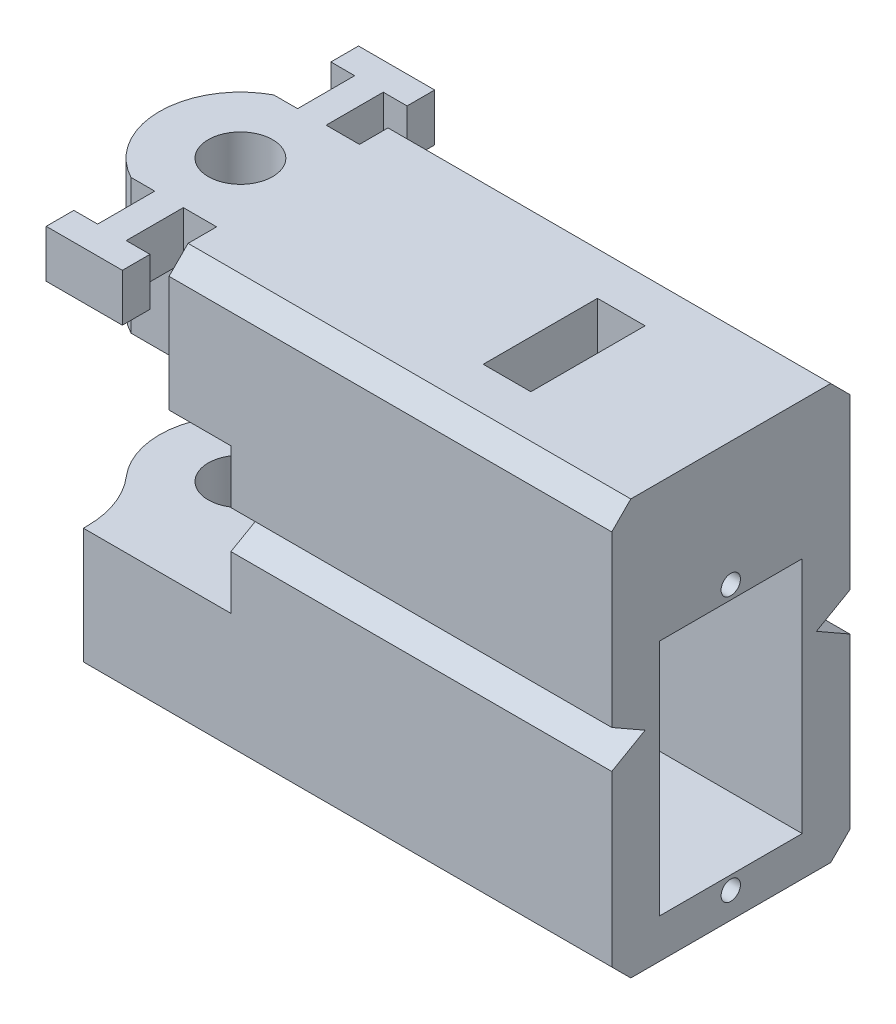
SolidWorks part; units mm, degrees
ref_plane "Front Plane" through (0, 0, 0) normal (0, 0, 1) x (1, 0, 0)
ref_plane "Top Plane" through (0, 0, 0) normal (0, 1, 0) x (1, 0, 0)
ref_plane "Right Plane" through (0, 0, 0) normal (1, 0, 0) x (0, 0, -1)
sketch "Sketch1" plane through (0, 0, 0) normal (1, 0, 0) x (0, 0, -1)
  line L0 (3.5, 21.787) -> (21.5, 21.787) construction
  line L1 (0, 0) -> (25, 0)
  line L2 (0, 0) -> (0, 19.787)
  line L3 (0, 43.574) -> (25, 43.574)
  line L4 (25, 0) -> (25, 19.787)
  line L5 (0, 23.787) -> (3.5, 21.787)
  line L6 (0, 19.787) -> (3.5, 21.787)
  line L7 (12.5, 43.574) -> (12.5, 0) construction
  line L8 (25, 23.787) -> (21.5, 21.787)
  line L9 (25, 19.787) -> (21.5, 21.787)
  line L10 (0, 23.787) -> (0, 43.574)
  line L11 (25, 23.787) -> (25, 43.574)
  point P6 (12.5, 21.787)
  dimension "D1" = 43.574
  dimension "D2" = 25
  dimension "D3" = 4
  dimension "D4" = 18
extrude "Boss-Extrude1" add sketch "Sketch1" along normal blind 55.5
chamfer "Chamfer1" distance 2 angle 45 4 edges at (27.75, 43.574, -25) (27.75, 43.574, 0) (27.75, 0, -25) (27.75, 0, 0)
sketch "Sketch4" plane through (0, 43.574, 0) normal (0, 1, 0) x (1, 0, 0)
  line L5 (0, 23) -> (0, 2) construction
  line L11 (0, 28.9) -> (8, 28.9)
  line L30 (0, 28.9) -> (0, -3.9)
  line L31 (0, -3.9) -> (8, -3.9)
  line L32 (8, 28.9) -> (8, -3.9)
  point P6 (0, 12.5)
  dimension "D1" = 32.8
  dimension "D2" = 8
extrude "Boss-Extrude2" add sketch "Sketch4" against normal blind 5
sketch "Sketch7" plane through (0, 43.574, 0) normal (0, 1, 0) x (1, 0, 0)
  line L0 (4, 28.9) -> (4, -3.9) construction
  line L1 (8, 28.9) -> (0, 28.9) construction
  line L2 (0, -3.9) -> (8, -3.9) construction
  line L3 (55.5, 12.5) -> (0, 12.5) construction
  line L4 (55.5, 23) -> (55.5, 2) construction
  line L5 (0, 28.9) -> (0, -3.9) construction
  line L6 (9, 5) -> (5.5, 5)
  line L7 (9, 26) -> (5.5, 26)
  line L8 (9, 26) -> (9, 20)
  line L9 (9, 20) -> (5.5, 20)
  line L10 (5.5, 26) -> (5.5, 20)
  line L11 (5.5, 23) -> (5.5, 12.5) construction
  line L12 (5.5, -1) -> (5.5, 5)
  line L13 (9, -1) -> (5.5, -1)
  line L14 (9, -1) -> (9, 5)
  line L15 (-1, -1) -> (-1, 5)
  line L16 (-1, -1) -> (2.5, -1)
  line L17 (2.5, -1) -> (2.5, 5)
  line L18 (-1, 5) -> (2.5, 5)
  line L19 (-1, 20) -> (2.5, 20)
  line L20 (2.5, 26) -> (2.5, 20)
  line L21 (-1, 26) -> (2.5, 26)
  line L22 (-1, 26) -> (-1, 20)
  dimension "D1" = 6
  dimension "D2" = 1.5
  dimension "D3" = 10.5
  dimension "D4" = 3.5
extrude "Cut-Extrude5" cut sketch "Sketch7" against normal blind 10
sketch "Sketch5" plane through (0, 43.574, 0) normal (0, 1, 0) x (1, 0, 0)
  line L0 (4, 28.9) -> (4, -3.9) construction
  line L1 (8, 28.9) -> (0, 28.9) construction
  line L2 (0, -3.9) -> (8, -3.9) construction
  circle A0 centre (4, 12.5) radius 1 construction
  circle A1 centre (4, 12.5) radius 3.375
  dimension "D1" = 2
  dimension "D2" = 6.75
extrude "Cut-Extrude3" cut sketch "Sketch5" against normal through all contours A1
ref_plane "Plane1" through (0, 21.787, 0) normal (0, -1, 0) x (-1, 0, 0)
sketch "Sketch6" plane through (0, 21.787, 0) normal (0, -1, 0) x (-1, 0, 0)
  line L6 (-4, 30) -> (4.5, 30)
  line L7 (4.5, 30) -> (4.5, -5)
  line L9 (4.5, -5) -> (-4, -5)
  line L10 (-15.5, -5) -> (-15.5, 30)
  line L11 (-15.5, 30) -> (-4, 30)
  line L12 (-15.5, -5) -> (-4, -5)
  circle A1 centre (-4, 12.5) radius 3.375 construction
  circle A5 centre (-4, 12.5) radius 3.375
  dimension "D1" = 15.5
  dimension "D2" = 20
  dimension "D3" = 35
  dimension "D4" = 17.5
extrude "Cut-Extrude4" cut sketch "Sketch6" against normal mid plane 15.24
sketch "Sketch8" plane through (0, 29.407, 0) normal (0, -1, 0) x (1, 0, 0)
  line L0 (9, 0) -> (9, -5) construction
  line L9 (9, -20) -> (9, -25) construction
  line L10 (9, 0) -> (9, -5)
  line L11 (9, -20) -> (9, -25)
  line L13 (9, -20) -> (0, -20)
  line L14 (9, -20) -> (9, -25)
  line L15 (9, -25) -> (0, -25)
  line L16 (0, -20) -> (0, -25)
  line L17 (9, -5) -> (0, -5)
  line L18 (9, -5) -> (9, 0)
  line L19 (9, 0) -> (0, 0)
  line L20 (0, -5) -> (0, 0)
  line M8 (15.5, 0) -> (0, 0)
  line M11 (0, 0) -> (0, -25)
  line M14 (0, -25) -> (15.5, -25)
extrude "Cut-Extrude6" cut sketch "Sketch8" against normal up to surface (9.167 mm away) contours L11 L13 M11 M14 | L17 L10 M8 M11 region at (4.5, 29.407, -22.5) region at (4.5, 29.407, -2.5) up to face at (4, 38.574, 1.475)
sketch "Sketch9" plane through (0, 43.574, 0) normal (0, 1, 0) x (1, 0, 0)
  line L0 (0, 20) -> (0, 5)
  arc A0 (0, 20) -> (0, 5) centre (4, 12.5) ccw
extrude "Boss-Extrude3" add sketch "Sketch9" against normal up to surface (14.167 mm away) up to face at (8.375, 29.407, -12.5)
extrude "Boss-Extrude4" add sketch "Sketch9<2>" along direction (0, 1, 0) on the side against the normal up to surface (43.574 mm away) from surface up to face at (4, 0, -9.125) starting at face at (4, 14.167, -15.875)
sketch "Sketch9<2>" plane through (0, 43.574, 0) normal (0, 1, 0) x (1, 0, 0) same geometry as "Sketch9"
fillet "Fillet1" radius 10 2 edges at (0, 7.0835, -20) (0, 7.0835, -5)
sketch "Sketch10" plane through (55.5, 0, 0) normal (1, 0, 0) x (0, 0, -1)
  line L0 (21.5, 21.787) -> (3.5, 21.787) construction
  line L1 (5, 29.137) -> (20, 29.137)
  line L2 (5, 29.137) -> (5, 4.137)
  line L3 (5, 4.137) -> (20, 4.137)
  line L4 (20, 29.137) -> (20, 4.137)
  line L5 (12.5, 43.574) -> (12.5, 4.137) construction
  line L6 (23, 43.574) -> (2, 43.574) construction
  line L8 (12.5, 29.137) -> (12.5, 21.787) construction
  line L9 (5, 16.637) -> (20, 16.637) construction
  circle A0 centre (12.5, 21.787) radius 2.5 construction
  point P22 (12.5, 25.462)
  dimension "D3" = 5
  dimension "D1" = 25
  dimension "D2" = 15
  dimension "D4" = 5.15
extrude "Cut-Extrude7" cut sketch "Sketch10" against normal blind 20
sketch "Sketch11" plane through (55.5, 0, 0) normal (1, 0, 0) x (0, 0, -1)
  line L0 (12.5, 43.574) -> (12.5, 30.537) construction
  line L1 (23, 43.574) -> (2, 43.574) construction
  line L2 (12.5, 30.537) -> (12.5, -0.3521) construction
  line L4 (5, 16.637) -> (20, 16.637) construction
  line L5 (5, 29.137) -> (5, 4.137) construction
  line L6 (20, 4.137) -> (20, 29.137) construction
  circle A0 centre (12.5, 30.537) radius 1.016
  circle A2 centre (12.5, 2.737) radius 1.016
  dimension "D2" = 2.032
  dimension "D1" = 8.75
extrude "Cut-Extrude8" cut sketch "Sketch11" against normal blind 8
sketch "Sketch12" plane through (0, 43.574, 0) normal (0, 1, 0) x (1, 0, 0)
  line L0 (40.5, 12.5) -> (55.5, 12.5) construction
  line L1 (40.5, 18.5) -> (35.5, 18.5)
  line L2 (40.5, 18.5) -> (40.5, 6.5)
  line L3 (40.5, 6.5) -> (35.5, 6.5)
  line L4 (55.5, 5) -> (55.5, 20)
  line L5 (35.5, 5) -> (55.5, 5)
  line L6 (35.5, 20) -> (35.5, 5)
  line L7 (55.5, 20) -> (35.5, 20)
  line L8 (55.5, 5) -> (55.5, 20)
  line L9 (35.5, 5) -> (55.5, 5)
  line L10 (35.5, 20) -> (35.5, 5)
  line L11 (55.5, 20) -> (35.5, 20)
  line L12 (35.5, 18.5) -> (35.5, 6.5)
  dimension "D2" = 15
  dimension "D3" = 12
  dimension "D1" = 0
extrude "Cut-Extrude9" cut sketch "Sketch12" against normal up to surface (14.437 mm away) contours L1 L10 L3 L2 region at (38, 43.574, -12.5) up to face at (45.5, 29.137, -12.5)
